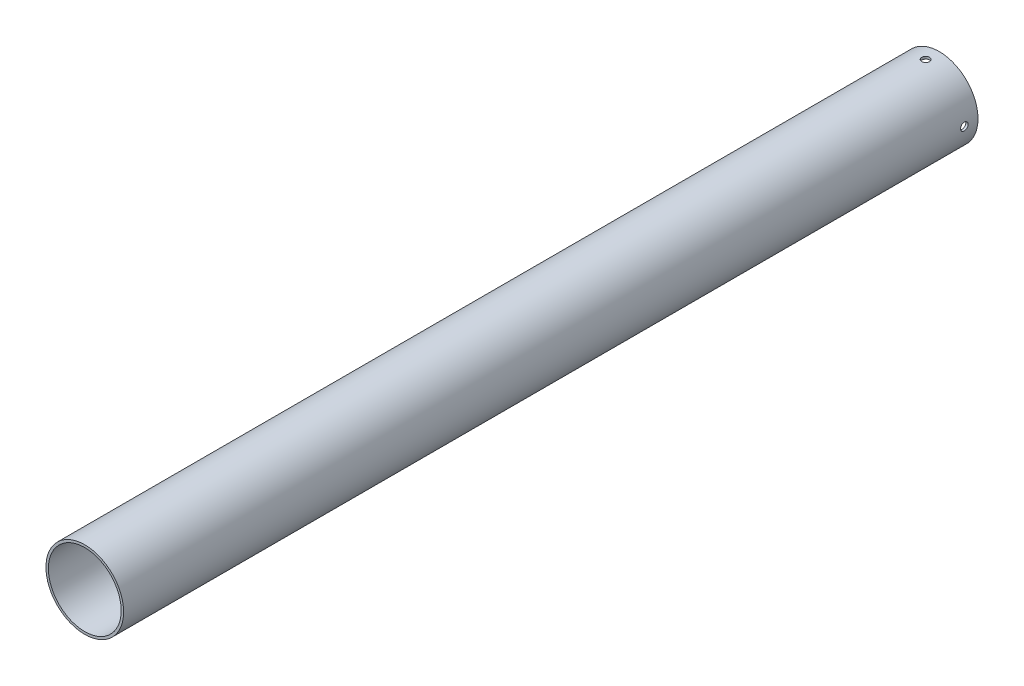
SolidWorks part; units mm, degrees
material "PC High Viscosity"
ref_plane "Front Plane" through (0, 0, 0) normal (0, 0, 1) x (1, 0, 0)
ref_plane "Top Plane" through (0, 0, 0) normal (0, 1, 0) x (1, 0, 0)
ref_plane "Right Plane" through (0, 0, 0) normal (1, 0, 0) x (0, 0, -1)
sketch "Sketch1" plane through (0, 0, 0) normal (0, 0, 1) x (1, 0, 0)
  circle A0 centre (0, 0) radius 23.8125
  circle A1 centre (0, 0) radius 25.4
  dimension "D1" = 50.8
  dimension "D2" = 47.625
extrude "Boss-Extrude1" add sketch "Sketch1" along normal mid plane 558.717
sketch "Sketch2" plane through (0, 0, 0) normal (1, 0, 0) x (0, 0, -1)
  line L0 (279.3585, -25.4) -> (279.3585, 25.4) construction
  circle A1 centre (270.4685, 0) radius 2.4892
  point P2 (0, 0)
  dimension "D1" = 4.9784
  dimension "D2" = 8.89
extrude "Cut-Extrude1" cut sketch "Sketch2" against normal through all both and the other way through all
sketch "Sketch3" plane through (0, 0, 0) normal (0, 1, 0) x (1, 0, 0)
  line L0 (25.4, 279.3585) -> (-25.4, 279.3585) construction
  circle A0 centre (0, 270.4685) radius 2.4892
  point P4 (0, 0)
  dimension "D1" = 4.9784
  dimension "D2" = 8.89
extrude "Cut-Extrude2" cut sketch "Sketch3" against normal through all both and the other way through all
equation "\"D1@Boss-Extrude1\"=21.125in+3.625mm"
